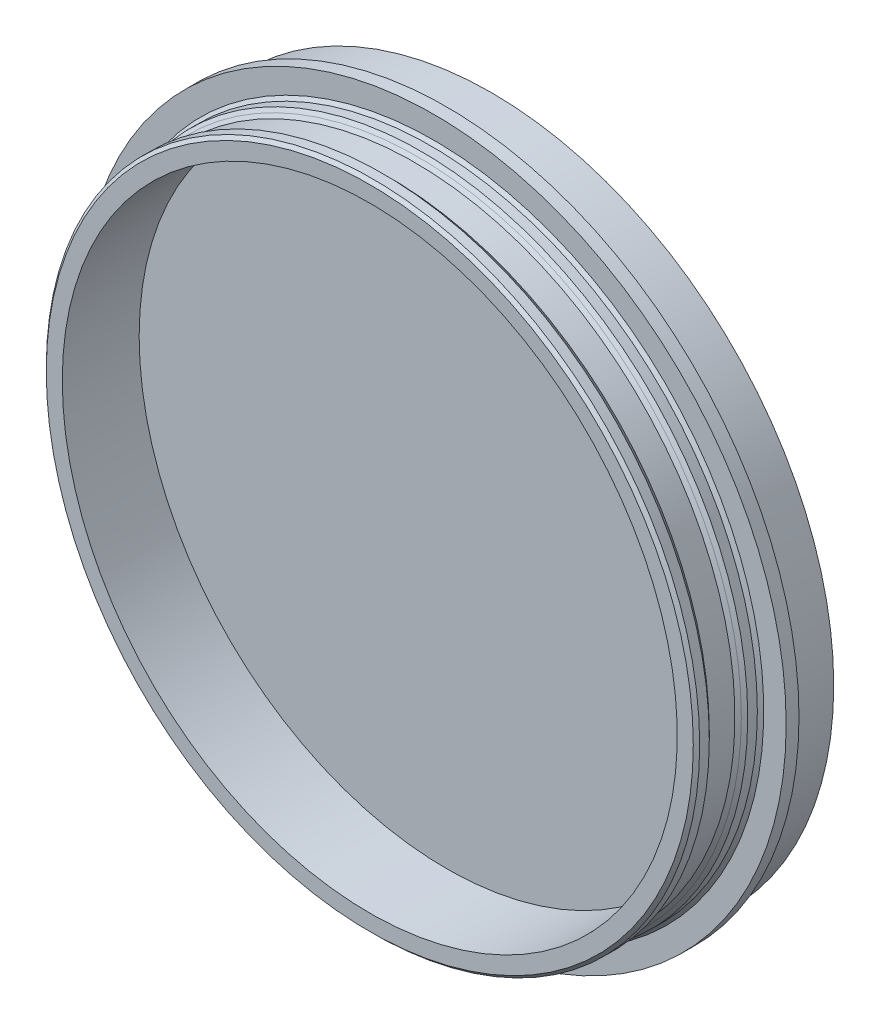
SolidWorks part; units mm, degrees
ref_plane "Front Plane" through (0, 0, 0) normal (0, 0, 1) x (1, 0, 0)
ref_plane "Top Plane" through (0, 0, 0) normal (0, 1, 0) x (1, 0, 0)
ref_plane "Right Plane" through (0, 0, 0) normal (1, 0, 0) x (0, 0, -1)
sketch "Sketch1" plane through (0, 0, 0) normal (0, 1, 0) x (1, 0, 0)
  line L0 (0, 69.1698) -> (0, -39.1508) construction
  line L1 (-62.5573, 0) -> (61.2977, 0) construction
  line L2 (50.425, 19) -> (50.425, 14)
  line L3 (50.425, 14) -> (48, 14)
  line L8 (51, 0) -> (51, 2.5)
  line L9 (51, 10) -> (55, 10)
  line L10 (55, 10) -> (55, 12)
  line L11 (55, 12) -> (53.425, 12)
  line L12 (53.425, 12) -> (53.425, 19)
  line L13 (53.425, 19) -> (50.425, 19)
  line L14 (51, 7.5) -> (50, 7.5)
  line L15 (50, 7.5) -> (50, 2.5)
  line L16 (50, 2.5) -> (51, 2.5)
  line L17 (51, 7.5) -> (51, 10)
  line L21 (48, 14) -> (48, 0)
  line L22 (48, 0) -> (51, 0)
  dimension "D1" = 55
  dimension "D3" = 53.425
  dimension "D4" = 3
  dimension "D5" = 5
  dimension "D6" = 7
  dimension "D7" = 3
  dimension "D8" = 51
  dimension "D9" = 2
  dimension "D10" = 10
  dimension "D12" = 1
  dimension "D13" = 5
  dimension "D14" = 2.5
revolve "Revolve1" add sketch "Sketch1" angle 360 about L0
chamfer "Chamfer1" distance 0.5 angle 45 8 edges at (-50, 0, -2.5) (-51, 0, -2.5) (-50, 0, -7.5) (-51, 0, -7.5) (-53.425, 0, -19) (-50.425, 0, -19) (-51, 0, -10) (-51, 0, 0)
sketch "Sketch2" plane through (0, 0, -12) normal (0, 0, -1) x (-1, 0, 0)
  circle A0 centre (0, 0) radius 53.425
  dimension "D1" = 106.85
extrude "Boss-Extrude1" add sketch "Sketch2" along normal up to surface (7 mm away) up to face at (52.925, 0, -19)
